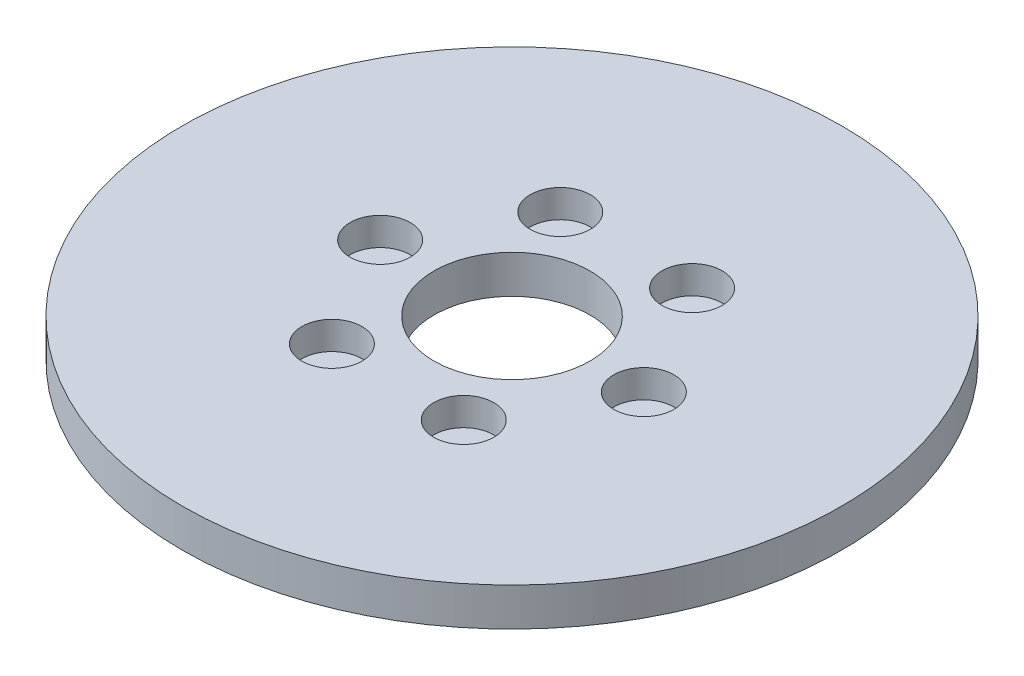
SolidWorks part; units mm, degrees
ref_plane "Front Plane" through (0, 0, 0) normal (0, 0, 1) x (1, 0, 0)
ref_plane "Top Plane" through (0, 0, 0) normal (0, 1, 0) x (1, 0, 0)
ref_plane "Right Plane" through (0, 0, 0) normal (1, 0, 0) x (0, 0, -1)
sketch "Sketch1" plane through (0, 0, 0) normal (0, 1, 0) x (1, 0, 0)
  circle A0 centre (0, 0) radius 95
  dimension "FLANGE_OD" = 190
extrude "Boss-Extrude1" add sketch "Sketch1" along normal blind 11
sketch "Sketch2" plane through (0, 0, 0) normal (0, 1, 0) x (1, 0, 0)
  circle A0 centre (0, 0) radius 22.5
  dimension "BORE_D" = 45
extrude "Cut-Extrude1" cut sketch "Sketch2" along normal through all
sketch "Sketch3" plane through (0, 11, 0) normal (0, 1, 0) x (1, 0, 0)
  circle A0 centre (0, 0) radius 38.0043 construction
  circle A1 centre (-38.0043, 0) radius 8.6661
  dimension "BOLT_D" = 17.3322
  dimension "BOLT_PCD" = 76.0087
extrude "Cut-Extrude2" cut sketch "Sketch3" against normal blind 8.0547
pattern_circular "CirPattern1" count 6 over 360 about axis through (0, 0, 0) along (0, 1, 0) of "Cut-Extrude2"
